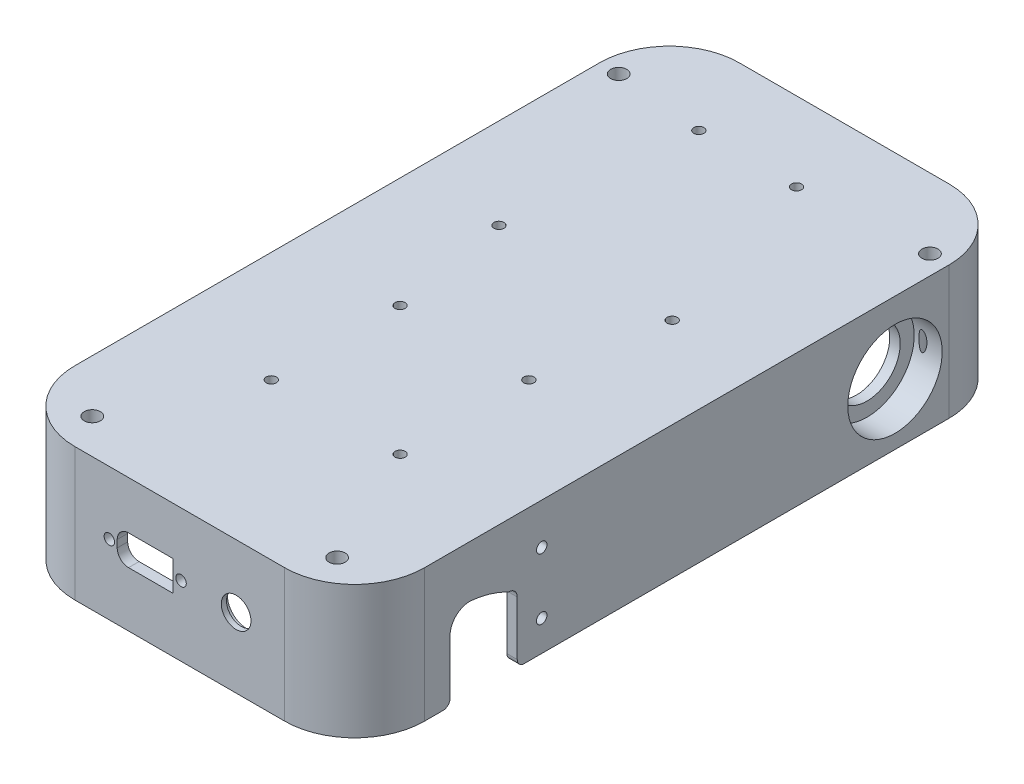
SolidWorks part; units mm, degrees
ref_plane "Front Plane" through (0, 0, 0) normal (0, 0, 1) x (1, 0, 0)
ref_plane "Top Plane" through (0, 0, 0) normal (0, 1, 0) x (1, 0, 0)
ref_plane "Right Plane" through (0, 0, 0) normal (1, 0, 0) x (0, 0, -1)
sketch "Sketch1" plane through (0, 0, 0) normal (0, 1, 0) x (1, 0, 0)
  line L0 (0, 20) -> (0, 170)
  line L1 (20, 0) -> (50, 0)
  line L3 (20, 190) -> (80, 190)
  line L24 (3, 90) -> (3, 23)
  line L32 (11, 130) -> (11, 185)
  line L45 (80, 0) -> (50, 0)
  line L46 (50, 190) -> (50, 0) construction
  line L47 (97, 90) -> (97, 23)
  line L48 (11, 130) -> (3, 90)
  line L49 (50, 190) -> (0, 190)
  line L50 (89, 130) -> (97, 90)
  line L51 (100, 20) -> (100, 170)
  line L52 (89, 130) -> (89, 185)
  line L53 (23, 3) -> (77, 3)
  line L54 (11, 185) -> (89, 185)
  line L55 (50, 170) -> (50, 101.42) construction
  line L56 (31.5875, 44.5875) -> (68.4125, 44.5875) construction
  line L57 (31.5875, 44.5875) -> (31.5875, 81.4125) construction
  line L58 (31.5875, 81.4125) -> (68.4125, 81.4125) construction
  line L59 (68.4125, 44.5875) -> (68.4125, 81.4125) construction
  line L60 (31.5875, 44.5875) -> (68.4125, 81.4125) construction
  line L61 (31.5875, 81.4125) -> (68.4125, 44.5875) construction
  line L62 (23.33, 170) -> (76.67, 170) construction
  line L63 (23.33, 170) -> (23.33, 101.42) construction
  line L64 (23.33, 101.42) -> (76.67, 101.42) construction
  line L65 (76.67, 170) -> (76.67, 101.42) construction
  line L66 (80, 10) -> (80, 3.2263)
  line L71 (5.5, 170) -> (94.5, 170) construction
  line L73 (85, 15) -> (95.3303, 15)
  line L74 (20, 10) -> (20, 3.2263)
  line L75 (15, 15) -> (4.6697, 15)
  line L76 (15, 10) -> (85, 10) construction
  circle A0 centre (31.5875, 81.4125) radius 1.45
  circle A1 centre (68.4125, 81.4125) radius 1.45
  circle A2 centre (68.4125, 44.5875) radius 1.45
  circle A3 centre (31.5875, 44.5875) radius 1.45
  circle A4 centre (31.5875, 81.4125) radius 2.25
  circle A5 centre (68.4125, 81.4125) radius 2.25
  circle A6 centre (68.4125, 44.5875) radius 2.25
  circle A7 centre (31.5875, 44.5875) radius 2.25
  circle A16 centre (74.13, 116.66) radius 1.45
  circle A17 centre (74.13, 116.66) radius 2.25
  circle A18 centre (25.87, 115.39) radius 1.45
  circle A19 centre (25.87, 115.39) radius 2.25
  circle A20 centre (30.95, 167.46) radius 2.25
  circle A21 centre (30.95, 167.46) radius 1.45
  circle A22 centre (58.89, 167.46) radius 1.45
  circle A23 centre (58.89, 167.46) radius 2.25
  circle A24 centre (5.5, 170) radius 2.3
  circle A25 centre (94.5, 170) radius 2.3
  circle A26 centre (85, 10) radius 2.3
  circle A27 centre (15, 10) radius 2.3
  arc A28 (77, 3) -> (97, 23) centre (77, 23) ccw
  arc A29 (80, 0) -> (100, 20) centre (80, 20) ccw
  arc A30 (0, 20) -> (20, 0) centre (20, 20) ccw
  arc A31 (23, 3) -> (3, 23) centre (23, 23) cw
  arc A32 (100, 170) -> (80, 190) centre (80, 170) ccw
  arc A33 (0, 170) -> (20, 190) centre (20, 170) cw
  arc A36 (85, 15) -> (80, 10) centre (85, 10) ccw
  arc A37 (20, 10) -> (15, 15) centre (15, 10) ccw
  point P13 (50, 63)
  point P61 (100, 0)
  point P70 (0, 0)
  point P76 (50, 10)
  point P78 (50, 170)
  point P80 (100, 190)
  dimension "D14" = 53.34
  dimension "D16" = 45.72
  dimension "D17" = 17.78
  dimension "D9" = 2.9
  dimension "D10" = 4.5
  dimension "D18" = 66.04
  dimension "D19" = 13.97
  dimension "D20" = 15.24
  dimension "D21" = 2.54
  dimension "D23" = 2.54
  dimension "D24" = 4.6
  dimension "D28" = 20
  dimension "D29" = 20
  dimension "D30" = 15
  dimension "D1" = 3
  dimension "D2" = 50
  dimension "D3" = 190
  dimension "D4" = 90
  dimension "D5" = 60
  dimension "D6" = 11
  dimension "D7" = 3
  dimension "D8" = 5
  dimension "D11" = 60
  dimension "D12" = 36.825
  dimension "D13" = 36.825
  dimension "D15" = 68.58
  dimension "D22" = 15
  dimension "D25" = 5.5
  dimension "D26" = 20
  dimension "D27" = 10
extrude "Boss-Extrude1" add sketch "Sketch1" along normal blind 3 contours L3 | A33 L0 A30 L1 L45 A29 L51 A32 L3 A24 A25 L53 A31 A27 L24 L48 L32 L54 L52 L50 L47 A28 A26 | A31 L53 A28 L47 L50 L52 L54 L32 L48 L24 A19 A17 A4 A5 A6 A7 A20 A23 | A28 A26 L47 | L24 A31 A27 | A20 A21 | A23 A22 | A17 A16 | A19 A18 | A4 A0 | A5 A1 | A7 A3 | A6 A2 region at (2.1471, 0, -95) region at (50.0105, 0, -92.0706) region at (9.8348, 0, -14.8067) region at (80.1933, 0, -6.6131) region at (29.4011, 0, -81.4125) region at (66.2261, 0, -81.4125) region at (66.2261, 0, -44.5875) region at (29.4011, 0, -44.5875) region at (71.9436, 0, -116.66) region at (23.6836, 0, -115.39) region at (28.7636, 0, -167.46) region at (56.7036, 0, -167.46)
extrude "Boss-Extrude2" add sketch "Sketch1<3>" against normal blind 35 contours A33 L0 A30 L1 L45 A29 L51 A32 L3 A24 A25 L53 A31 L24 L48 L32 L54 L52 L50 L47 A28 | L74 A37 L75 A31 A27 | L73 A36 L66 A28 A26 region at (2.1471, 0, -95) region at (9.8348, 0, -14.8067) region at (80.1933, 0, -6.6131)
sketch "Sketch1<3>" plane through (0, 0, 0) normal (0, 1, 0) x (1, 0, 0) same geometry as "Sketch1"
sketch "Sketch2" plane through (0, 0, 0) normal (-1, 0, 0) x (0, 0, 1)
  line L0 (-53.5, -8.75) -> (-53.5, -26.25) construction
  line L1 (-46.5, -35) -> (-27.285, -35)
  line L2 (0, -35) -> (0, 0) construction
  line L3 (-20, -35) -> (-170, -35) construction
  line L4 (-154.5, -17.5) -> (-33, -17.5) construction
  line L9 (-63.5, -14.9) -> (-66, -14.9) construction
  line L10 (-27.285, -17.5) -> (-27.285, -35)
  line L11 (-20, -35) -> (-170, -35) construction
  line L12 (-63.5, -14.9) -> (-63.5, -35) construction
  line L13 (-63.5, -35) -> (-66, -35) construction
  line L14 (-46.5, -17.5) -> (-46.5, -35)
  line L15 (-66, -14.9) -> (-66, -35) construction
  line L16 (-67, -13.9) -> (-67, -35)
  line L18 (-62.5, -13.9) -> (-62.5, -35)
  line L19 (-62.5, -13.9) -> (-67, -13.9)
  line L20 (-67, -35) -> (-62.5, -35)
  line L21 (-67, -13.9) -> (-67, -36) construction
  line L22 (-62.5, -13.9) -> (-62.5, -36) construction
  line L23 (-190, 3) -> (-190, -35) construction
  line L24 (-20, 3) -> (-20, -35) construction
  line L25 (-62.5, -36) -> (-67, -36) construction
  circle A0 centre (-33, -17.5) radius 5.715
  circle A1 centre (-53.5, -8.75) radius 1.5
  circle A2 centre (-53.5, -26.25) radius 1.5
  circle A3 centre (-154.5, -17.5) radius 13.5
  circle A6 centre (-44, -17.5) radius 2.5
  circle A7 centre (-154.5, -17.5) radius 33.5 construction
  circle A8 centre (-33, -17.5) radius 33.5 construction
  circle A9 centre (-154.5, -17.5) radius 9.5
  spline S0 degree 2 poles (-44, -15) (-38.6612, -12.2662) (-33, -11.785) knots 0 0 0 0.700659 0.700659 0.700659
  point P8 (-53.5, -17.5)
  point P11 (0, -17.5)
  line M36 (-170, -35) -> (-20, -35)
  dimension "D1" = 3
  dimension "D3" = 20.5
  dimension "D4" = 0
  dimension "D5" = 13
  dimension "D6" = 11.43
  dimension "D7" = 4
  dimension "D8" = 27
  dimension "D9" = 11
  dimension "D10" = 5
  dimension "D11" = 67
  dimension "D12" = 2
  dimension "D2" = 17.5
  dimension "D13" = 8.5
  dimension "D14" = 2.5
  dimension "D15" = 2.6
  dimension "D16" = 1
extrude "Cut-Extrude1" cut sketch "Sketch2" against normal through all both and the other way through all contours A9 | S0 A6 L14 L10 A0 M36 | S0 A0 | A6 | A1 | A2 region at (0, -26.8802, -37.5218) region at (0, -17.5, -44) region at (0, -17.5011, -32.9999) region at (0, -8.75, -53.5) region at (0, -26.25, -53.5) region at (0, -17.5, -154.5)
extrude "Cut-Extrude2" cut sketch "Sketch2<5>" against normal blind 8 contours A3 A9 region at (0, -17.5, -167.6182)
sketch "Sketch2<5>" plane through (0, 0, 0) normal (-1, 0, 0) x (0, 0, 1) same geometry as "Sketch2"
extrude "Cut-Extrude3" cut sketch "Sketch2<6>" along normal blind 8 from surface contours A3 A9 region at (0, -17.5, -167.6182) starting at face at (100, -17.5, -145)
sketch "Sketch2<6>" plane through (0, 0, 0) normal (-1, 0, 0) x (0, 0, 1) same geometry as "Sketch2"
sketch "Sketch3" plane through (0, 0, -190) normal (0, 0, -1) x (-1, 0, 0)
  line L0 (-50, -35) -> (-50, 3) construction
  line L1 (-20, -35) -> (-80, -35) construction
  line L2 (-20, 3) -> (-80, 3) construction
  line L3 (-63.65, -15) -> (-36.35, -15) construction
  line L4 (-11, 0) -> (-89, 0) construction
  circle A0 centre (-36.35, -15) radius 8.5
  circle A1 centre (-63.65, -15) radius 8.5
  point P9 (-50, -15)
  dimension "D2" = 17
  dimension "D1" = 10.3
  dimension "D3" = 15
extrude "Cut-Extrude4" cut sketch "Sketch3" against normal up to next
fillet "Fillet2" radius 5 2 edges at (89, -17.5, -185) (11, -17.5, -185)
extrude "Boss-Extrude3" add sketch "Sketch1<7>" against normal blind 3.5 contours A4 A0 | A7 A3 | A6 A2 | A5 A1 | A23 A22 | A20 A21 | A19 A18 | A17 A16 region at (29.4011, 0, -81.4125) region at (66.2261, 0, -81.4125) region at (66.2261, 0, -44.5875) region at (29.4011, 0, -44.5875) region at (71.9436, 0, -116.66) region at (23.6836, 0, -115.39) region at (28.7636, 0, -167.46) region at (56.7036, 0, -167.46)
sketch "Sketch1<7>" plane through (0, 0, 0) normal (0, 1, 0) x (1, 0, 0) same geometry as "Sketch1"
fillet "Fillet3" radius 2 12 edges at (31.5875, 0, -42.3375) (68.4125, 0, -42.3375) (68.4125, 0, -79.1625) (31.5875, 0, -79.1625) (25.87, 0, -113.14) (74.13, 0, -114.41) (30.95, 0, -165.21) (58.89, 0, -165.21) (98.5, -35, -27.285) (98.5, -35, -46.5) (1.5, -35, -46.5) (1.5, -35, -27.285)
sketch "Sketch4" plane through (0, 0, 0) normal (0, 0, 1) x (1, 0, 0)
  line L0 (29.875, -15) -> (50.375, -15) construction
  line L2 (35.375, -19.05) -> (47.875, -19.05) construction
  line L3 (32.375, -16.05) -> (32.375, -13.95) construction
  line L4 (35.375, -10.95) -> (47.875, -10.95) construction
  line L5 (47.875, -19.05) -> (47.875, -10.95) construction
  line L6 (32.375, -19.05) -> (47.875, -10.95) construction
  line L7 (32.375, -10.95) -> (47.875, -19.05) construction
  line L8 (32.125, -16.05) -> (32.125, -13.95)
  line L12 (35.375, -10.7) -> (48.125, -10.7)
  line L13 (48.125, -19.3) -> (48.125, -10.7)
  line L14 (35.375, -19.3) -> (48.125, -19.3)
  line L15 (28.375, -15) -> (71.625, -15) construction
  line L16 (20, 3) -> (80, 3) construction
  line L17 (23, 0) -> (77, 0) construction
  circle A0 centre (29.875, -15) radius 1.5
  circle A1 centre (50.375, -15) radius 1.5
  arc A4 (35.375, -19.05) -> (32.375, -16.05) centre (35.375, -16.05) cw construction
  arc A5 (32.375, -13.95) -> (35.375, -10.95) centre (35.375, -13.95) cw construction
  arc A6 (32.125, -13.95) -> (35.375, -10.7) centre (35.375, -13.95) cw
  arc A7 (35.375, -19.3) -> (32.125, -16.05) centre (35.375, -16.05) cw
  circle A8 centre (66.125, -15) radius 4.25
  circle A9 centre (66.125, -15) radius 5.5
  point P3 (40.125, -15)
  point P5 (40.125, -15)
  point P29 (50, 3)
  point P32 (50, -15)
  dimension "D2" = 3
  dimension "D6" = 8.5
  dimension "D7" = 3
  dimension "D10" = 10
  dimension "D11" = 11
  dimension "D1" = 20.5
  dimension "D3" = 15.5
  dimension "D4" = 8.1
  dimension "D5" = 15
  dimension "D8" = 0.25
extrude "Cut-Extrude5" cut sketch "Sketch4" against normal up to next contours A7 L14 L13 L12 A6 L8 | A0 | A1 | A8 region at (40.3728, -15, 0) region at (29.875, -15, 0) region at (50.375, -15, 0) region at (66.125, -15, 0)
extrude "Cut-Extrude6" cut sketch "Sketch4<5>" along normal blind 1.5 from surface contours A9 A8 region at (60.7806, -15, 0) starting at face at (70.375, -15, -3)
sketch "Sketch4<5>" plane through (0, 0, 0) normal (0, 0, 1) x (1, 0, 0) same geometry as "Sketch4"
extrude "Cut-Extrude7" cut sketch "Sketch2<8>" along normal blind 1.5 from surface contours L18 L19 L16 M36 region at (0, -24.45, -64.75) starting at face at (3, -26.25, -52)
sketch "Sketch2<8>" plane through (0, 0, 0) normal (-1, 0, 0) x (0, 0, 1) same geometry as "Sketch2"
extrude "Cut-Extrude8" cut sketch "Sketch2<9>" against normal blind 1.5 from surface contours L18 L19 L16 M36 region at (0, -24.45, -64.75) starting at face at (97, -26.25, -52)
sketch "Sketch2<9>" plane through (0, 0, 0) normal (-1, 0, 0) x (0, 0, 1) same geometry as "Sketch2"
